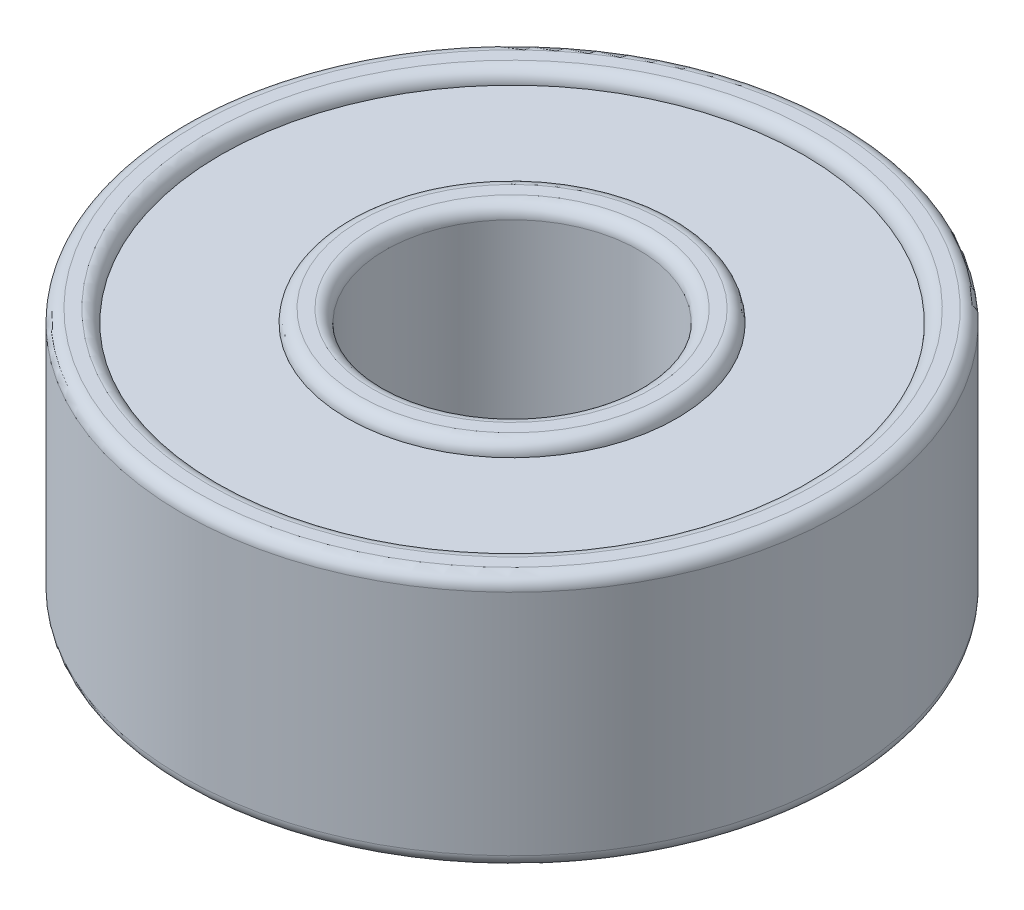
SolidWorks part; units mm, degrees
ref_plane "正面" through (0, 0, 0) normal (0, 0, 1) x (1, 0, 0)
ref_plane "平面" through (0, 0, 0) normal (0, 1, 0) x (1, 0, 0)
ref_plane "右側面" through (0, 0, 0) normal (1, 0, 0) x (0, 0, -1)
sketch "ｽｹｯﾁ1" plane through (0, 0, 0) normal (0, 1, 0) x (1, 0, 0)
  circle A0 centre (0, 0) radius 2.5
  circle A1 centre (0, 0) radius 6.5
  dimension "D1" = 5
  dimension "D2" = 13
extrude "ﾎﾞｽ - 押し出し1" add sketch "ｽｹｯﾁ1" along normal mid plane 5
sketch "ｽｹｯﾁ2" plane through (0, 2.5, 0) normal (0, 1, 0) x (1, 0, 0)
  circle A2 centre (0, 0) radius 5.75
  circle A3 centre (0, 0) radius 5.75
  circle A5 centre (0, 0) radius 3.25
  circle A6 centre (0, 0) radius 3.25
  dimension "D1" = 0.75
  dimension "D2" = 0.75
extrude "ｶｯﾄ - 押し出し1" cut sketch "ｽｹｯﾁ2" against normal mid plane 0.5
mirror "ﾐﾗｰ1" about plane through (0, 0, 0) normal (0, 1, 0) of "ｶｯﾄ - 押し出し1"
fillet "ﾌｨﾚｯﾄ1" radius 0.25
